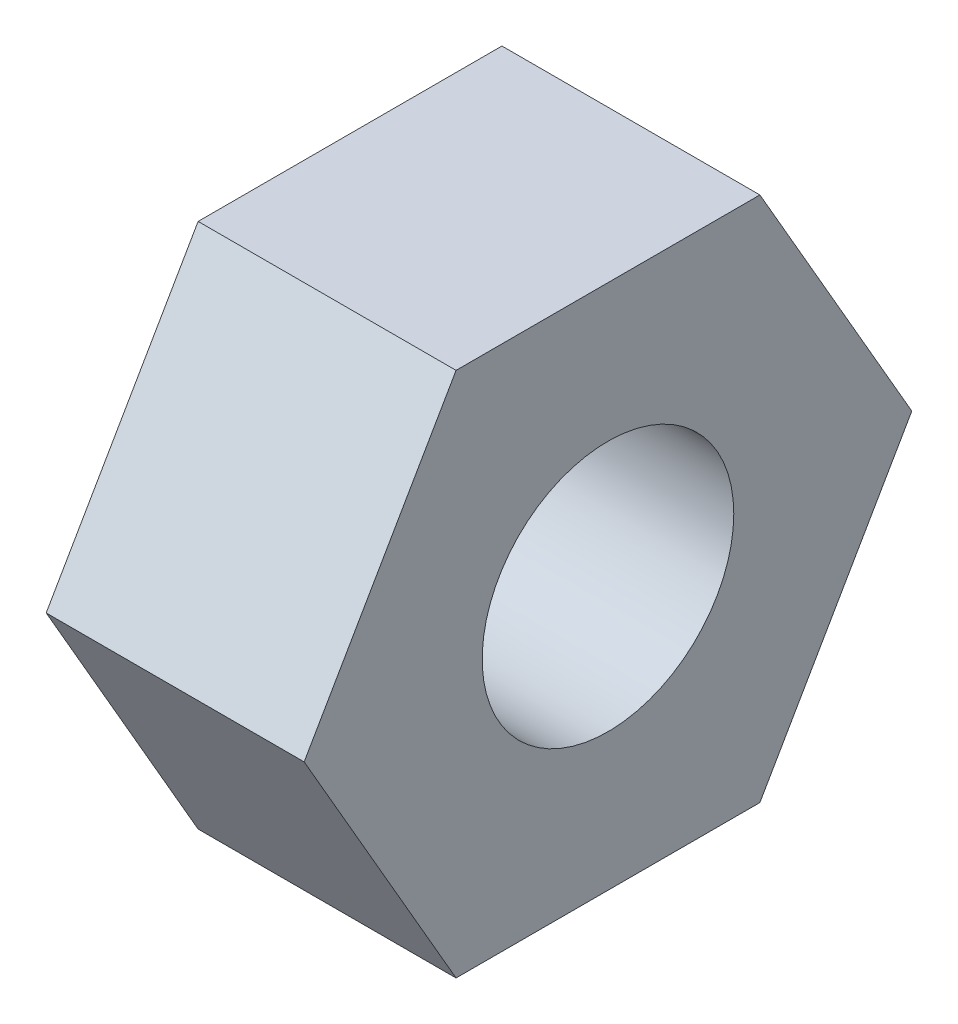
SolidWorks part; units mm, degrees
material "6061-T4 (SS)"
ref_plane "Front Plane" through (0, 0, 0) normal (0, 0, 1) x (1, 0, 0)
ref_plane "Top Plane" through (0, 0, 0) normal (0, 1, 0) x (1, 0, 0)
ref_plane "Right Plane" through (0, 0, 0) normal (1, 0, 0) x (0, 0, -1)
sketch "Sketch1" plane through (0, 0, 0) normal (1, 0, 0) x (0, 0, -1)
  line L0 (0, 0) -> (2.9445, 0) construction
  line L1 (2.9445, 0) -> (1.4722, 2.55)
  line L2 (1.4722, 2.55) -> (-1.4722, 2.55)
  line L3 (-1.4722, 2.55) -> (-2.9445, 0)
  line L4 (-2.9445, 0) -> (-1.4722, -2.55)
  line L5 (-1.4722, -2.55) -> (1.4722, -2.55)
  line L6 (1.4722, -2.55) -> (2.9445, 0)
  circle A0 centre (0, 0) radius 2.55 construction
  point P1 (-2.2084, 1.275)
  dimension "D1" = 5.1
extrude "Boss-Extrude1" add sketch "Sketch1" along normal blind 2.5
sketch "Sketch2" plane through (2.5, 0, 0) normal (1, 0, 0) x (0, 0, -1)
  circle A0 centre (0, 0) radius 1.0922
  dimension "D1" = 2.1844
hole_wizard "#2 Clearance Hole1" positions "Sketch3" profile "Sketch4" hole size "#2" standard "ANSI Inch" end condition through all
sketch "Sketch3" plane through (2.5, 0, 0) normal (1, 0, 0) x (0, 0, -1)
  point P0 (0, 0)
sketch "Sketch4" plane through (2.5, 0, 0) normal (0, 1, 0) x (0, 0, -1)
  line L0 (0, 0) -> (0, 2.5)
  line L1 (0, 2.5) -> (1.2192, 2.5)
  line L2 (1.2192, 2.5) -> (1.2192, 0)
  line L5 (1.2192, 0) -> (0, 0)
  line L11 (0, -6.35) -> (0, 107.95) construction
  dimension "Thru Hole Dia." = 2.4384
  dimension "Thru Hole Depth" = 2.5
